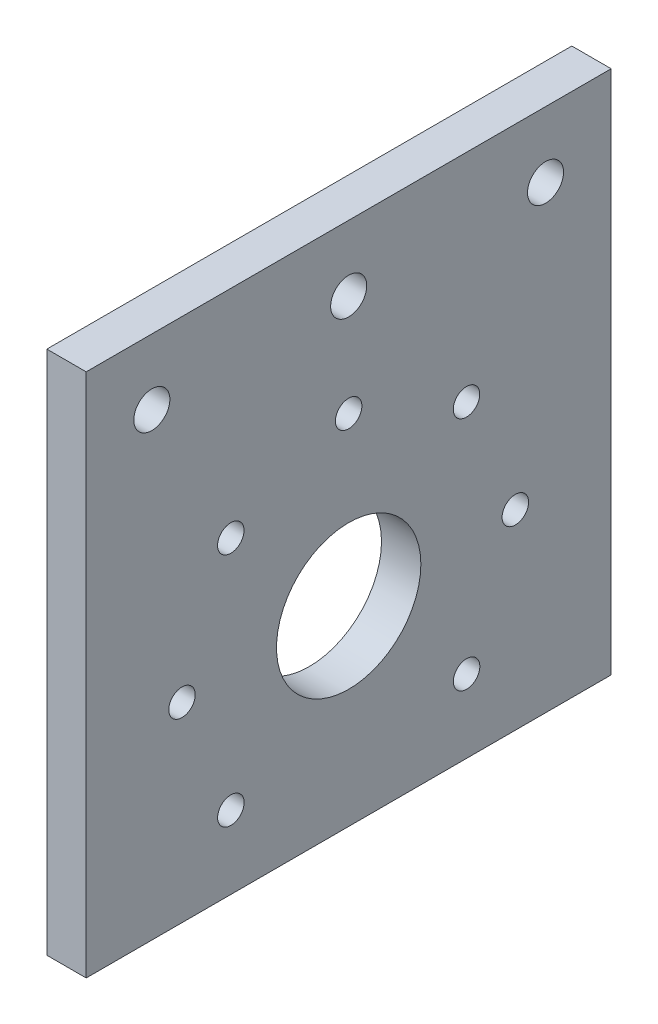
SolidWorks part; units mm, degrees
ref_plane "Front Plane" through (0, 0, 0) normal (0, 0, 1) x (1, 0, 0)
ref_plane "Top Plane" through (0, 0, 0) normal (0, 1, 0) x (1, 0, 0)
ref_plane "Right Plane" through (0, 0, 0) normal (1, 0, 0) x (0, 0, -1)
sketch "Sketch1" plane through (0, 0, 0) normal (1, 0, 0) x (0, 0, -1)
  line L1 (-28.2506, 24.9879) -> (51.7494, 24.9879)
  line L2 (-28.2506, 24.9879) -> (-28.2506, -55.0121)
  line L3 (-28.2506, -55.0121) -> (51.7494, -55.0121)
  line L4 (51.7494, 24.9879) -> (51.7494, -55.0121)
  dimension "D1" = 80
  dimension "D2" = 80
extrude "Boss-Extrude1" add sketch "Sketch1" along normal blind 6
sketch "Sketch2" plane through (6, 0, 0) normal (1, 0, 0) x (0, 0, -1)
  line L0 (51.7494, 24.9879) -> (-28.2506, 24.9879) construction
  line L2 (-28.2506, 24.9879) -> (-28.2506, -55.0121) construction
  line L3 (51.7494, -55.0121) -> (51.7494, 24.9879) construction
  circle A0 centre (11.7494, -25.9119) radius 11
  circle A1 centre (-18.2506, 14.9879) radius 2.75
  circle A2 centre (41.7494, 14.9879) radius 2.75
  circle A3 centre (11.7494, 14.9879) radius 2.75
  point P6 (0, 0)
  point P11 (0, 0)
  point P12 (0, 0)
  point P13 (11.7494, 24.9879)
  point P14 (0, 0)
  point P15 (0, 0)
  point P16 (0, 0)
  point P17 (0, 0)
  point P20 (11.7494, -25.9119)
  point P23 (0, 0)
  point P24 (11.7494, -18.6046)
  dimension "D1" = 22
  dimension "D2" = 5.5
  dimension "D3" = 5.5
  dimension "D5" = 5.5
  dimension "D4" = 10
  dimension "D6" = 10
  dimension "D7" = 10
extrude "Cut-Extrude1" cut sketch "Sketch2" against normal through all
sketch "Sketch3" plane through (0, 0, 0) normal (-1, 0, 0) x (0, 0, 1)
  circle A0 centre (-37.1494, -25.9041) radius 2.0193 construction
  circle A1 centre (13.6506, -25.9196) radius 2.0193 construction
  circle A2 centre (6.2166, -7.9568) radius 2.0193 construction
  circle A3 centre (-29.7044, -7.9459) radius 2.0193 construction
  circle A4 centre (-11.7417, -0.5119) radius 2.0193 construction
  circle A5 centre (-37.1494, -25.9041) radius 2.0193
  circle A6 centre (13.6506, -25.9196) radius 2.0193
  circle A7 centre (6.2166, -7.9568) radius 2.0193
  circle A8 centre (-29.7044, -7.9459) radius 2.0193
  circle A9 centre (-11.7417, -0.5119) radius 2.0193
  circle A10 centre (6.2057, -43.8778) radius 2.0193 construction
  circle A11 centre (-29.7154, -43.8669) radius 2.0193 construction
  circle A12 centre (6.2057, -43.8778) radius 2.0193
  circle A13 centre (-29.7154, -43.8669) radius 2.0193
extrude "Cut-Extrude2" cut sketch "Sketch3" against normal through all
